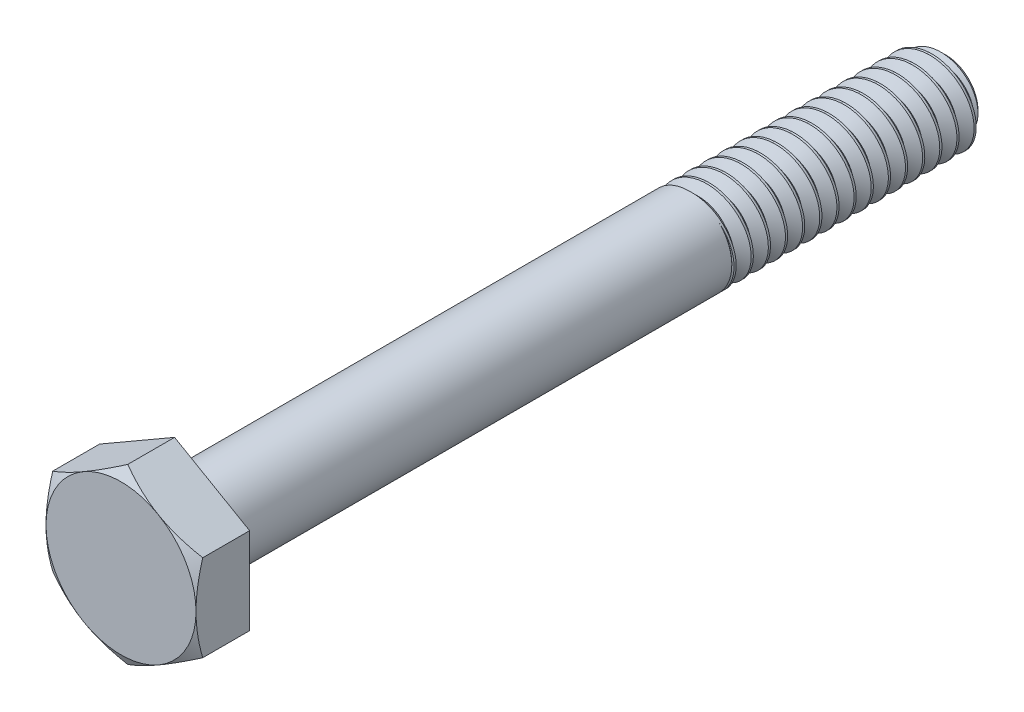
SolidWorks part; units mm, degrees
material "AISI 304"
ref_plane "Front Plane" through (0, 0, 0) normal (0, 0, 1) x (1, 0, 0)
ref_plane "Top Plane" through (0, 0, 0) normal (0, 1, 0) x (1, 0, 0)
ref_plane "Right Plane" through (0, 0, 0) normal (1, 0, 0) x (0, 0, -1)
sketch "Sketch1" plane through (0, 0, 0) normal (0, 0, 1) x (1, 0, 0)
  line L1 (0, 6.4158) -> (-5.5563, 3.2079) construction
  line L2 (-5.5563, 3.2079) -> (-5.5562, -3.2079) construction
  line L3 (-5.5562, -3.2079) -> (0, -6.4158) construction
  line L4 (0, -6.4158) -> (5.5563, -3.2079) construction
  line L5 (5.5563, -3.2079) -> (5.5562, 3.2079) construction
  line L6 (5.5562, 3.2079) -> (0, 6.4158) construction
  circle A0 centre (0, 0) radius 5.5562 construction
  point P10 (-5.5563, 3.2079)
  point P11 (5.5562, 3.2079)
  point P12 (0, -6.4158)
  point P13 (5.5563, -3.2079)
  point P14 (0, 6.4158)
  point P15 (-5.5562, -3.2079)
  dimension "Head Width" = 11.1125
sketch "Sketch2" plane through (0, 0, 0) normal (1, 0, 0) x (0, 0, -1)
  line L0 (30.5594, 0) -> (-30.5594, 0) construction
  line L1 (30.5594, 2.36) -> (30.5594, 3.3125) construction
  line L2 (30.5594, -3.175) -> (30.5594, 3.175) construction
  line L3 (-30.5594, -6.4158) -> (-30.5594, 6.4158) construction
  line L4 (-26.5906, -6.4158) -> (-26.5906, 6.4158) construction
  line L5 (30.5594, 3.175) -> (-26.5906, 3.175) construction
  line L6 (30.5594, -3.175) -> (-26.5906, -3.175) construction
  line L7 (-30.5594, -6.4158) -> (-26.5906, -6.4158) construction
  line L8 (-30.5594, 6.4158) -> (-26.5906, 6.4158) construction
  line L9 (11.5094, -3.175) -> (11.5094, 3.175) construction
  line L10 (30.48, 3.3125) -> (31.75, 3.3125) construction
  line L11 (31.75, 3.3125) -> (31.115, 2.2126) construction
  line L12 (31.115, 2.2126) -> (30.48, 3.3125) construction
  line L13 (30.5197, 3.2437) -> (31.7103, 3.2437) construction
  line L14 (30.5594, 3.175) -> (31.6706, 3.175) construction
  line L15 (31.0356, 2.3501) -> (31.1944, 2.3501) construction
  line L16 (31.115, 2.3501) -> (31.115, 2.2126) construction
  line L17 (31.115, 3.175) -> (31.115, 3.3125) construction
  line L18 (30.5594, 3.3125) -> (29.6069, 3.3125) construction
  line L19 (29.6069, 3.3125) -> (30.5594, 2.36) construction
  point P0 (27.3844, -3.175)
  point P3 (0, 0)
  point P7 (30.5594, 0)
  point P10 (-30.5594, 0)
  point P15 (-26.5906, 0)
  point P16 (-26.5906, 6.4158)
  point P17 (-30.5594, 6.4158)
  point P18 (30.5594, 3.175)
  point P19 (30.5594, -3.175)
  point P22 (-26.5906, 3.175)
  point P23 (-26.5906, -3.175)
  point P24 (-26.5906, -6.4158)
  point P25 (-30.5594, -6.4158)
  point P28 (11.5094, 0)
  point P29 (11.5094, 3.175)
  point P30 (11.5094, -3.175)
  point P41 (31.115, 3.175)
  point P44 (31.115, 3.2437)
  dimension "D2" = 0.1588
  dimension "D1" = 3.175
  dimension "D3" = 0.9525
  dimension "D4" = 45
ref_plane "Plane1" through (0, 0, -11.5094) normal (0, 0, 1) x (1, 0, 0)
sketch "Sketch3" plane through (0, 0, 0) normal (1, 0, 0) x (0, 0, -1)
  line L0 (-26.5906, -6.4158) -> (-26.5906, 6.4158) construction
  line L1 (30.5594, 0) -> (-30.5594, 0) construction
  line L2 (30.5594, -3.175) -> (30.5594, 3.175) construction
  line L3 (29.6069, 3.3125) -> (30.5594, 2.36) construction
  line L4 (30.5594, 3.175) -> (-26.5906, 3.175) construction
  line L5 (-26.5906, 0) -> (-26.5906, 3.175)
  line L6 (30.5594, 0) -> (-26.5906, 0)
  line L7 (30.5594, 0) -> (30.5594, 2.36)
  line L8 (29.7444, 3.175) -> (30.5594, 2.36)
  line L9 (29.7444, 3.175) -> (-26.5906, 3.175)
revolve "Revolve1" add sketch "Sketch3" angle 360 about L6
sketch "Sketch4" plane through (0, 0, 26.5906) normal (0, 0, 1) x (1, 0, 0)
  line L0 (-5.5563, 3.2079) -> (-5.5562, -3.2079) construction
  line L1 (-5.5562, -3.2079) -> (0, -6.4158) construction
  line L2 (0, -6.4158) -> (5.5563, -3.2079) construction
  line L3 (5.5563, -3.2079) -> (5.5562, 3.2079) construction
  line L4 (5.5562, 3.2079) -> (0, 6.4158) construction
  line L5 (0, 6.4158) -> (-5.5563, 3.2079) construction
  line L6 (-5.5563, 3.2079) -> (-5.5562, -3.2079)
  line L7 (-5.5562, -3.2079) -> (0, -6.4158)
  line L8 (0, -6.4158) -> (5.5563, -3.2079)
  line L9 (5.5563, -3.2079) -> (5.5562, 3.2079)
  line L10 (5.5562, 3.2079) -> (0, 6.4158)
  line L11 (0, 6.4158) -> (-5.5563, 3.2079)
extrude "Boss-Extrude1" add sketch "Sketch4" along normal up to vertex (3.9688 mm away) up to point (0, 6.4158, 30.5594)
sketch "Sketch5" plane through (0, 0, 30.5594) normal (0, 0, 1) x (1, 0, 0)
  circle A0 centre (0, 0) radius 5.5562 construction
  circle A1 centre (0, 0) radius 5.5562
extrude "Cut-Extrude1" cut sketch "Sketch5" against normal through all draft 60 flip side to cut
sketch "Sketch6" plane through (0, 0, -30.5594) normal (0, 0, -1) x (-1, 0, 0)
  circle A0 centre (0, 0) radius 3.175
curve "Helix/Spiral1" pitch 1.27 height 20.32 radius 3.175 centre (0, 0, -30.5594) axis (0, 0, 1) start towards (0, 1, 0)
sketch "Sketch7" plane through (0, 0, 0) normal (1, 0, 0) x (0, 0, -1)
  line L0 (31.0356, 2.3501) -> (31.1944, 2.3501) construction
  line L1 (30.5197, 3.2437) -> (31.7103, 3.2437) construction
  line L2 (31.0356, 2.3501) -> (31.1944, 2.3501)
  line L3 (30.5197, 3.2437) -> (31.7103, 3.2437)
  line L4 (31.75, 3.3125) -> (31.115, 2.2126) construction
  line L5 (31.115, 2.2126) -> (30.48, 3.3125) construction
  line L6 (31.7103, 3.2437) -> (31.1944, 2.3501)
  line L7 (31.0356, 2.3501) -> (30.5197, 3.2437)
sweep "Cut-Sweep1" cut profiles "Sketch7" path "Helix/Spiral1" align with end faces yes
sketch "Sketch8" plane through (0, 0, -11.5094) normal (0, 0, 1) x (1, 0, 0)
  circle A0 centre (0, 0) radius 3.175
extrude "Boss-Extrude2" add sketch "Sketch8" along normal up to vertex and the other way through all draft 45 up to point (0, 0, 26.5906)
equation "\"D2@Sketch2\" = \"Thread Pitch@Sketch2\" / 8"
equation "\"D1@Sketch2\"=\"Thread Pitch@Sketch2\"*2.5"
equation "\"D3@Sketch2\"=\"Thread Pitch@Sketch2\"*.75"
equation "\"D3@Helix/Spiral1\"=\"Minimum Thread Length@Sketch2\"+\"Thread Pitch@Sketch2\""
equation "\"D4@Helix/Spiral1\"=\"Thread Pitch@Sketch2\""
